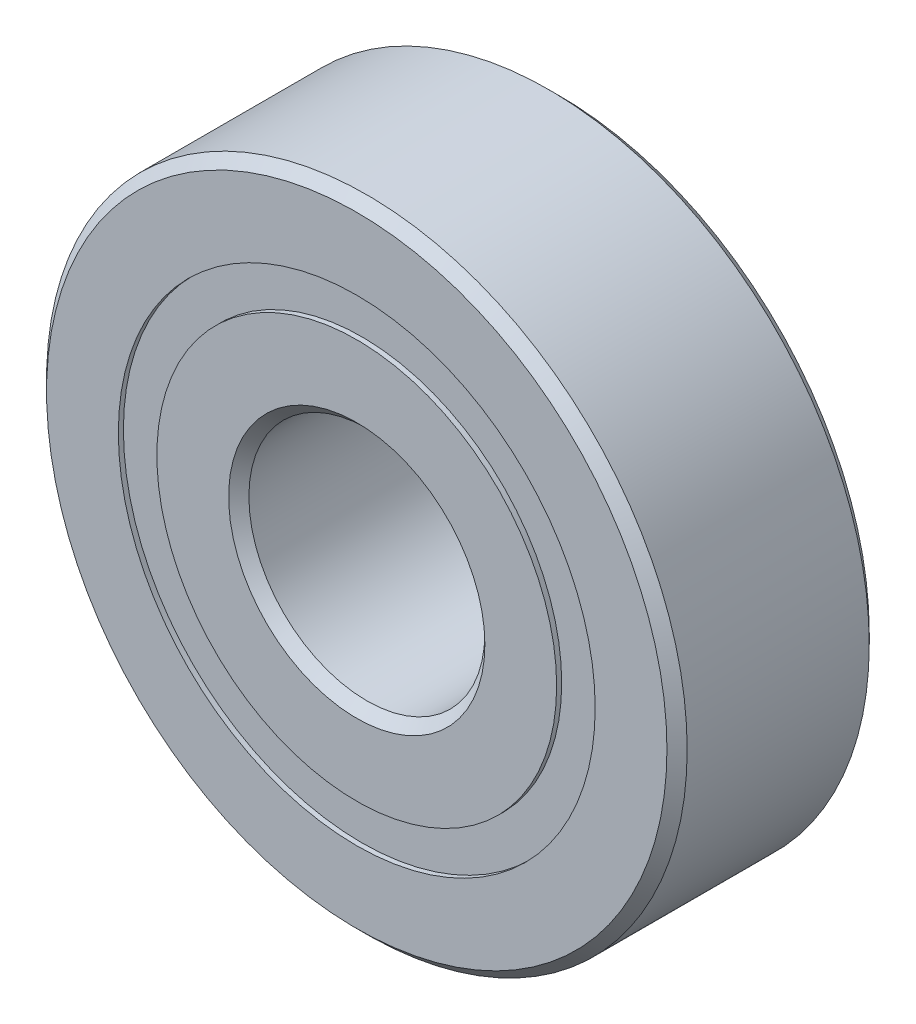
SolidWorks part; units mm, degrees
ref_plane "Front Plane" through (0, 0, 0) normal (0, 0, 1) x (1, 0, 0)
ref_plane "Top Plane" through (0, 0, 0) normal (0, 1, 0) x (1, 0, 0)
ref_plane "Right Plane" through (0, 0, 0) normal (1, 0, 0) x (0, 0, -1)
sketch "Sketch1" plane through (0, 0, 0) normal (1, 0, 0) x (0, 0, -1)
  line L0 (-3, 0) -> (3, 0) construction
  line L1 (0, 9.5) -> (0, -9.5) construction
  line L2 (2.7, 9.5) -> (-2.7, 9.5)
  line L3 (-2.7, 9.5) -> (-3, 9.2)
  line L4 (-3, 9.2) -> (-3, 7.0714)
  line L5 (-3, 7.0714) -> (-1.3333, 7.0714)
  line L6 (3, 7.0714) -> (1.3333, 7.0714)
  line L7 (3, 9.2) -> (3, 7.0714)
  line L8 (2.7, 9.5) -> (3, 9.2)
  line L9 (0, 9.5) -> (0, 6.5) construction
  line L10 (0, 6.5) -> (0, 3.5) construction
  arc A0 (-1.3333, 7.0714) -> (1.3333, 7.0714) centre (0, 6.5) cw
  point P14 (0, 3.5)
  dimension "D3" = 2.6667
  dimension "D1" = 45
  dimension "Width" = 6
  dimension "OD" = 19
  dimension "D2" = 0.3
  dimension "Shaft Dia" = 7
  dimension "D4" = 0.5714
revolve "Revolve1" add sketch "Sketch1" angle 360 about L0
sketch "Sketch3" plane through (0, 0, 0) normal (1, 0, 0) x (0, 0, -1)
  line L0 (-3, 5.9286) -> (-1.3333, 5.9286)
  line L1 (0, 9.5) -> (0, -9.5) construction
  line L2 (-3, 9.2) -> (-3, 7.0714) construction
  line L3 (-3, 5.9286) -> (-3, 3.8)
  line L4 (-2.7, 9.5) -> (-3, 9.2) construction
  line L5 (-3, 3.8) -> (-2.7, 3.5)
  line L6 (-2.7, 3.5) -> (2.7, 3.5)
  line L7 (2.7, 9.5) -> (2.7, -9.5) construction
  line L8 (2.7, 3.5) -> (3, 3.8)
  line L9 (3, -9.2) -> (3, 9.2) construction
  line L10 (3, 3.8) -> (3, 5.9286)
  line L11 (3, 5.9286) -> (1.3333, 5.9286)
  line L13 (2.7, 9.5) -> (3, 9.2) construction
  arc A0 (1.3333, 7.0714) -> (-1.3333, 7.0714) centre (0, 6.5) ccw construction
  arc A1 (1.3333, 5.9286) -> (-1.3333, 5.9286) centre (0, 6.5) cw
revolve "Revolve3" add sketch "Sketch3" angle 360 about L0
sketch "Sketch4" plane through (0, 0, 0) normal (1, 0, 0) x (0, 0, -1)
  line L0 (-1.4506, 6.5) -> (1.4506, 6.5)
  arc A2 (-1.4506, 6.5) -> (1.4506, 6.5) centre (0, 6.5) cw
  arc A3 (1.3333, 7.0714) -> (-1.3333, 7.0714) centre (0, 6.5) ccw construction
revolve "Revolve4" add sketch "Sketch4" angle 360 about L0
ref_axis "Axis1" through (0, 0, -3) along (0, 0, 1)
pattern_circular "CirPattern1" count 12 every 30 about axis through (0, 0, -3) along (0, 0, 1) of bodies 104
sketch "Sketch5" plane through (0, 0, 0) normal (1, 0, 0) x (0, 0, -1)
  line L0 (-3, 7.0714) -> (-1.3333, 7.0714) construction
  line L1 (-2.85, 7.0714) -> (-1.4506, 7.0714)
  line L2 (-2.85, 7.0714) -> (-2.85, 5.9286)
  line L3 (-2.85, 5.9286) -> (-1.4506, 5.9286)
  line L4 (-1.4506, 7.0714) -> (-1.4506, 5.9286)
  line L5 (-3, 5.9286) -> (-1.3333, 5.9286) construction
  line L6 (3, 7.0714) -> (1.3333, 7.0714) construction
  line L7 (2.85, 7.0714) -> (1.4506, 7.0714)
  line L8 (2.85, 7.0714) -> (2.85, 5.9286)
  line L9 (2.85, 5.9286) -> (1.4506, 5.9286)
  line L10 (1.4506, 7.0714) -> (1.4506, 5.9286)
  line L11 (3, 5.9286) -> (1.3333, 5.9286) construction
  line L12 (-2.7, 9.5) -> (-3, 9.2) construction
  point P18 (-2.85, 9.35)
revolve "Revolve5" add sketch "Sketch5" angle 360 about L0
equation "\"D2@Sketch1\" = \"Width@Sketch1\"*.05"
equation "\"D3@Sketch1\" = \"Width@Sketch1\"/2.25"
equation "\"D4@Sketch1\" = (((\"OD@Sketch1\"-\"Width@Sketch1\")/2)/3.25)/3.5"
equation "\"D2@CirPattern1\" = 360/\"Balls@CirPattern1\""
